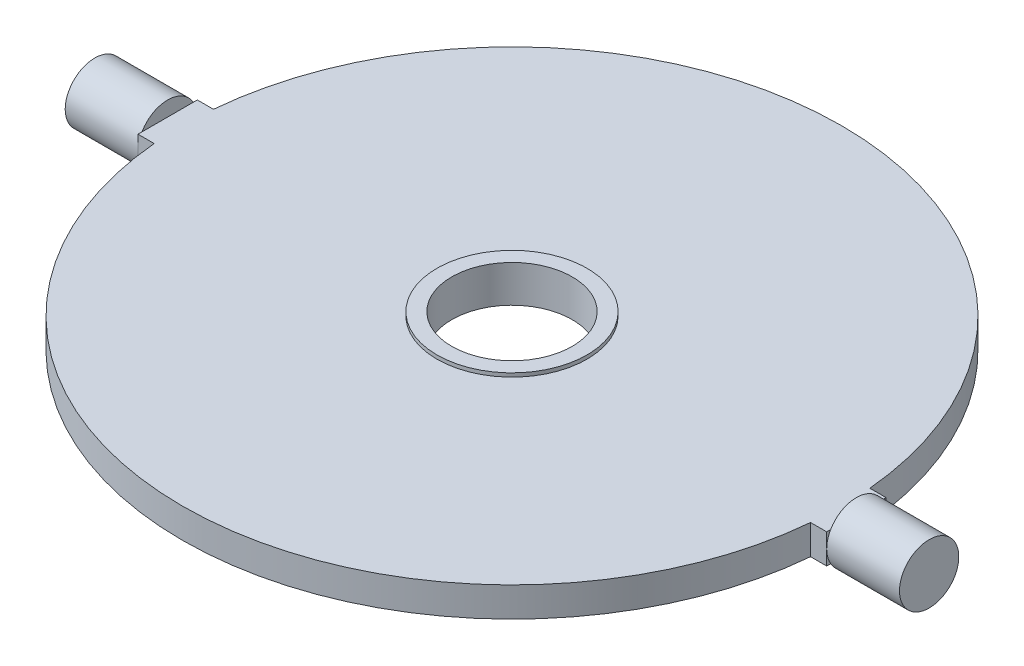
SolidWorks part; units mm, degrees
ref_plane "Front Plane" through (0, 0, 0) normal (0, 0, 1) x (1, 0, 0)
ref_plane "Top Plane" through (0, 0, 0) normal (0, 1, 0) x (1, 0, 0)
ref_plane "Right Plane" through (0, 0, 0) normal (1, 0, 0) x (0, 0, -1)
sketch "Sketch1" plane through (0, 0, 0) normal (0, 1, 0) x (1, 0, 0)
  line L0 (-76.4354, 0) -> (76.4354, 0) construction
  line L1 (-56.2697, 4) -> (-56.2697, -4)
  line L2 (0, 44.45) -> (0, -44.45) construction
  line L3 (-56.2697, 4) -> (-44.2697, 4)
  line L4 (-56.2697, -4) -> (-44.2697, -4)
  line L5 (56.2697, -4) -> (44.2697, -4)
  line L6 (56.2697, 4) -> (56.2697, -4)
  line L7 (56.2697, 4) -> (44.2697, 4)
  line L8 (-56.2697, 0) -> (-44.45, 0)
  line L9 (56.2697, 0) -> (44.45, 0)
  line L10 (46.45, 4) -> (46.45, -4)
  line L11 (-46.45, 4) -> (-46.45, -4)
  circle A0 centre (0, 0) radius 44.45
  circle A1 centre (0, 0) radius 8.125
  circle A2 centre (0, 0) radius 10.125
  point P6 (0, 0)
  point P9 (-56.2697, 0)
  dimension "D1" = 88.9
  dimension "D4" = 16.25
  dimension "D2" = 8
  dimension "D3" = 12
  dimension "D6" = 2
  dimension "D5" = 2
extrude "Boss-Extrude1" add sketch "Sketch1" along normal mid plane 4 contours A0 | A0 L3 L11 L8 | A0 L8 L11 L4 | A0 L9 L10 L7 | A0 L5 L10 L9 region at (-45.4193, 0, -2.0292) region at (-45.4193, 0, 2.0292) region at (0, 0, -43.1928) region at (45.4193, 0, -2.0292) region at (45.4193, 0, 2.0292)
revolve "Revolve1" add sketch "Sketch1<6>" angle 360 about L0 region at (-51.3598, 0, 2) region at (51.3598, 0, 2)
sketch "Sketch1<6>" plane through (0, 0, 0) normal (0, 1, 0) x (1, 0, 0) same geometry as "Sketch1"
extrude "Boss-Extrude2" add sketch "Sketch1<7>" along normal mid plane 5 contours A2 A1 region at (-9.8386, 0, 0)
sketch "Sketch1<7>" plane through (0, 0, 0) normal (0, 1, 0) x (1, 0, 0) same geometry as "Sketch1"
